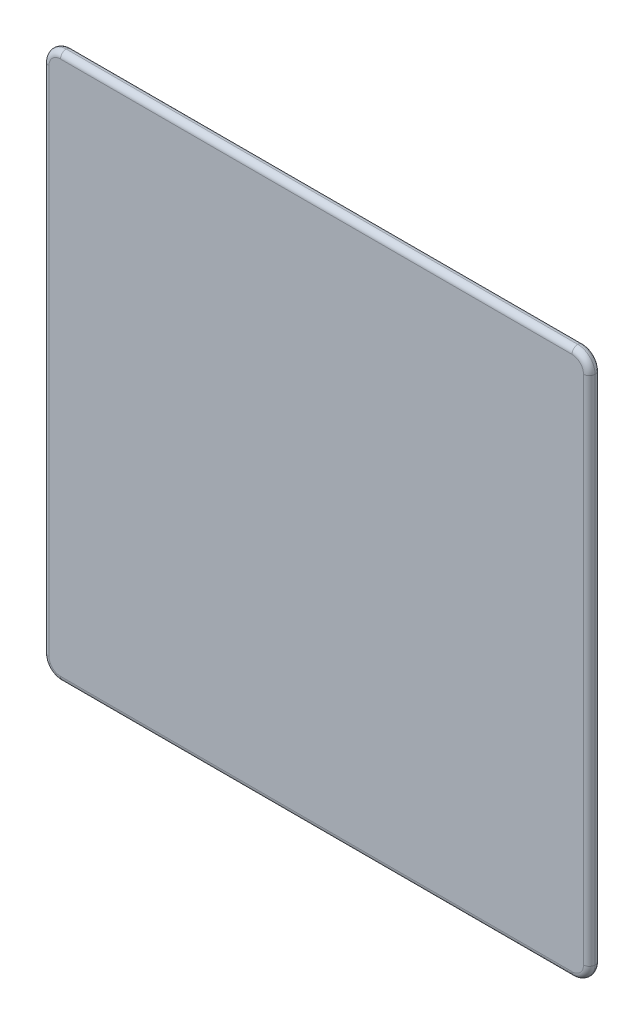
SolidWorks part; units mm, degrees
ref_plane "Front Plane" through (0, 0, 0) normal (1, 0, 0) x (0, 1, 0)
ref_plane "Top Plane" through (0, 0, 0) normal (0, 0, 1) x (0, 1, 0)
ref_plane "Right Plane" through (0, 0, 0) normal (0, 1, 0) x (-1, 0, 0)
sketch "Sketch1" plane through (0, 0, 0) normal (0, 0, 1) x (0, 1, 0)
  line L1 (47.4, -47.4) -> (-47.4, -47.4)
  line L2 (47.4, -47.4) -> (47.4, 47.4)
  line L3 (47.4, 47.4) -> (-47.4, 47.4)
  line L4 (-47.4, -47.4) -> (-47.4, 47.4)
  line L5 (47.4, -47.4) -> (-47.4, 47.4) construction
  line L6 (47.4, 47.4) -> (-47.4, -47.4) construction
  point P0 (0, 0)
  dimension "D1" = 94.8
  dimension "D2" = 94.8
extrude "Boss-Extrude1" add sketch "Sketch1" along normal blind 2
fillet "Fillet1" radius 3 4 edges at (-47.4, 47.4, 1) (-47.4, -47.4, 1) (47.4, -47.4, 1) (47.4, 47.4, 1)
ref_plane "mid plane" through (0, 0, 1) normal (0, 0, 1) x (0, -1, 0)
fillet "Fillet2" radius 1 16 edges at (46.5213, 46.5213, 0) (47.4, 0, 0) (46.5213, -46.5213, 0) (0, -47.4, 0) (-46.5213, -46.5213, 0) (-47.4, 0, 0) (-46.5213, 46.5213, 0) (46.5213, 46.5213, 2) (47.4, 0, 2) (46.5213, -46.5213, 2) (0, -47.4, 2) (-46.5213, -46.5213, 2) (-47.4, 0, 2) (-46.5213, 46.5213, 2) (0, 47.4, 2) (0, 47.4, 0)
equation "\"D2@Sketch1\"=\"D1@Sketch1\""
